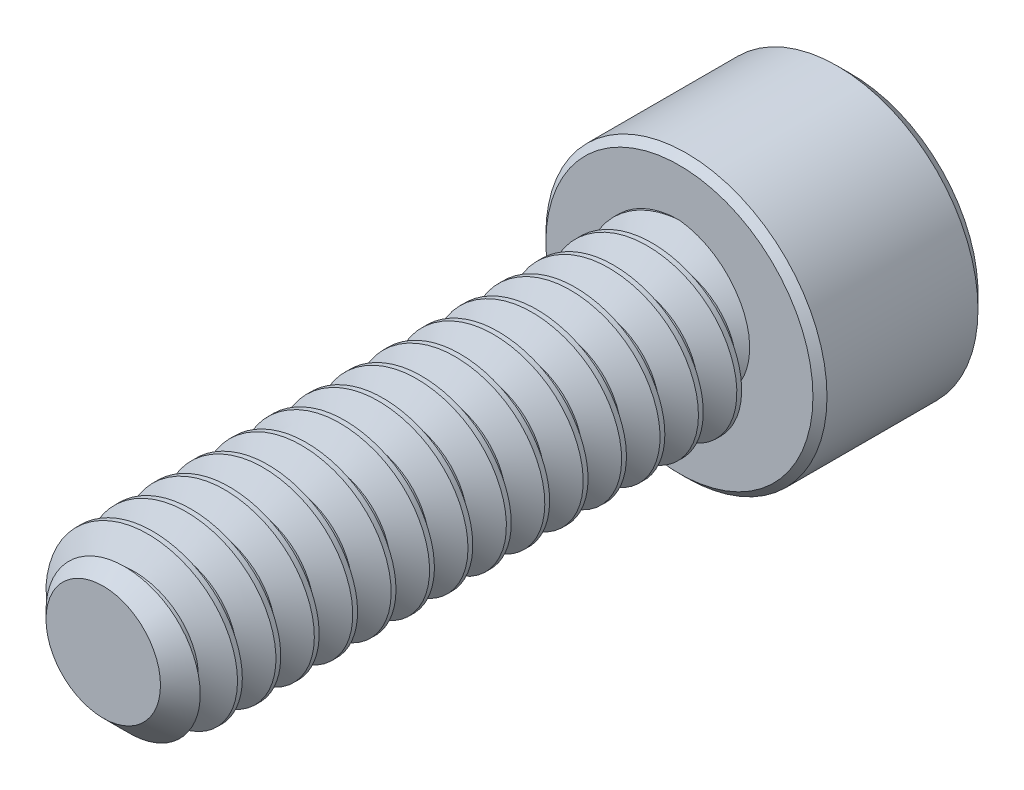
SolidWorks part; units mm, degrees
material "Cast Stainless Steel"
ref_plane "Front Plane" through (0, 0, 0) normal (0, 0, 1) x (1, 0, 0)
ref_plane "Top Plane" through (0, 0, 0) normal (0, 1, 0) x (1, 0, 0)
ref_plane "Right Plane" through (0, 0, 0) normal (1, 0, 0) x (0, 0, -1)
sketch "Sketch0" plane through (0, 0, 0) normal (1, 0, 0) x (0, 0, -1)
  line L0 (0, 0) -> (9.525, 0) construction
  point P2 (12.3698, 0)
  point P4 (0, 0)
  dimension "D1" = 9.525
  dimension "D2" = 2.8448
  dimension "Min Thread" = 0
sketch "Sketch1" plane through (0, 0, 0) normal (0, 0, 1) x (1, 0, 0)
  circle A0 centre (0, 0) radius 1.4224
  dimension "OD" = 2.8448
extrude "Extrude1" add sketch "Sketch1" against normal blind 9.525
sketch "Sketch2" plane through (0, 0, 0) normal (0, 0, 1) x (1, 0, 0)
  circle A0 centre (0, 0) radius 1.4224 construction
  circle A1 centre (0, 0) radius 1.4224
curve "Helix/Spiral1" pitch 0.635 height 10.16 radius 1.4224 centre (0, 0, 0) axis (0, 0, -1) start towards (0, 1, 0) parameters "pitch"=0.635
chamfer "Chamfer3" distance 0.4763 angle 45 1 edges at (1.4224, 0, 0)
sketch "Sketch3" plane through (0, 0, 0) normal (1, 0, 0) x (0, 0, -1)
  line L0 (-0.5556, 1.4224) -> (-0.3175, 1.01)
  line L1 (-0.3175, 1.01) -> (-0.2381, 1.01)
  line L2 (-0.2381, 1.01) -> (0, 1.4224)
  line L3 (-0.5556, 1.4224) -> (0, 1.4224)
  line L4 (-0.2778, 1.4224) -> (-0.2778, 1.01) construction
  line L5 (-0.4366, 1.2162) -> (-0.1191, 1.2162) construction
  line L6 (0, 1.4224) -> (0, -1.4224) construction
  dimension "D1" = 0.0794
  dimension "D2" = 0.3175
  dimension "D3" = 60
sweep "Cut-Sweep1" cut profiles "Sketch3" path "Helix/Spiral1"
sketch "Sketch5" plane through (0, 0, 0) normal (1, 0, 0) x (0, 0, -1)
  line L0 (9.525, -1.0232) -> (9.525, 1.0149) construction
  line L1 (9.525, 1.4224) -> (0, 1.4224)
  line L2 (9.525, 1.4224) -> (9.525, 0)
  line L3 (9.525, 0) -> (-0.5177, 0)
  line L4 (0, 0) -> (9.525, 0) construction
  line L5 (0, 1.4224) -> (-0.5177, 0)
  line L6 (0, 0) -> (12.065, 0) construction
  dimension "D1" = 70
  dimension "D3" = 2.54
revolve "partially thread" [suppressed] add sketch "Sketch5" angle 360 about L6
sketch "Sketch6" plane through (0, 0, -9.525) normal (0, 0, -1) x (-1, 0, 0)
  circle A0 centre (0, 0) radius 2.3241
  dimension "head dia" = 4.6482
extrude "Extrude2" add sketch "Sketch6" along normal blind 2.8448
sketch "Sketch7" plane through (0, 0, -12.3698) normal (0, 0, -1) x (-1, 0, 0)
  line L1 (0, 1.3748) -> (-1.1906, 0.6874)
  line L2 (-1.1906, 0.6874) -> (-1.1906, -0.6874)
  line L3 (-1.1906, -0.6874) -> (0, -1.3748)
  line L4 (0, -1.3748) -> (1.1906, -0.6874)
  line L5 (1.1906, -0.6874) -> (1.1906, 0.6874)
  line L6 (1.1906, 0.6874) -> (0, 1.3748)
  circle A0 centre (0, 0) radius 1.1906 construction
  dimension "hex dia" = 2.3813
extrude "Cut-Extrude1" cut sketch "Sketch7" against normal blind 1.7859
sketch "Sketch8" plane through (0, 0, -12.3698) normal (0, 0, -1) x (-1, 0, 0)
  circle A0 centre (0, 0) radius 1.3748
extrude "Cut-Extrude2" cut sketch "Sketch8" against normal through all draft 45
chamfer "Chamfer1" distance 0.2324 angle 45 1 edges at (-2.3241, 0, -12.3698)
chamfer "Chamfer2" distance 0.1162 angle 45 1 edges at (-2.3241, 0, -9.525)
sketch "Sketch9" plane through (0, 0, 0) normal (1, 0, 0) x (0, 0, -1)
  line L0 (0, 1.4224) -> (0, -1.4224) construction
  line L1 (1.5875, 1.4224) -> (1.5875, -1.4224) construction
  line L2 (12.3698, 2.3241) -> (12.3698, -2.3241) construction
  line L3 (9.525, 2.3241) -> (9.525, -2.3241) construction
  line L4 (9.525, 2.2079) -> (9.525, -2.2079) construction
  line L5 (12.3698, -2.0917) -> (12.3698, 2.0917) construction
  line L6 (9.525, -2.3241) -> (9.525, 2.3241) construction
  line L7 (0, 0.9462) -> (0, -0.9462) construction
  line L8 (-0.5556, 1.4224) -> (0, 1.4224) construction
  line L9 (1.5875, 0) -> (0, 0) construction
  dimension "D1" = 1.5875
equation "\"D3@Helix/Spiral1\" = \"screw length@Extrude1\"+\"pitch@Helix/Spiral1\""
equation "\"D1@Sketch3\" = \"pitch@Helix/Spiral1\"*.125"
equation "\"D2@Sketch3\" = \"pitch@Helix/Spiral1\"*.5"
equation "\"D1@Cut-Extrude1\" = \"hex dia@Sketch7\"*.75"
equation "\"D1@Chamfer1\" = \"head dia@Sketch6\"*.05"
equation "\"D1@Sketch9\" = \"pitch@Helix/Spiral1\"*2.50"
equation "\"D1@Chamfer2\" = \"D1@Chamfer1\"/2"
equation "\"D1@Chamfer3\" = \"pitch@Helix/Spiral1\"*.750"
equation "\"D1@Sketch0\" = \"screw length@Extrude1\""
equation "\"D2@Sketch0\" = \"head depth@Extrude2\""
